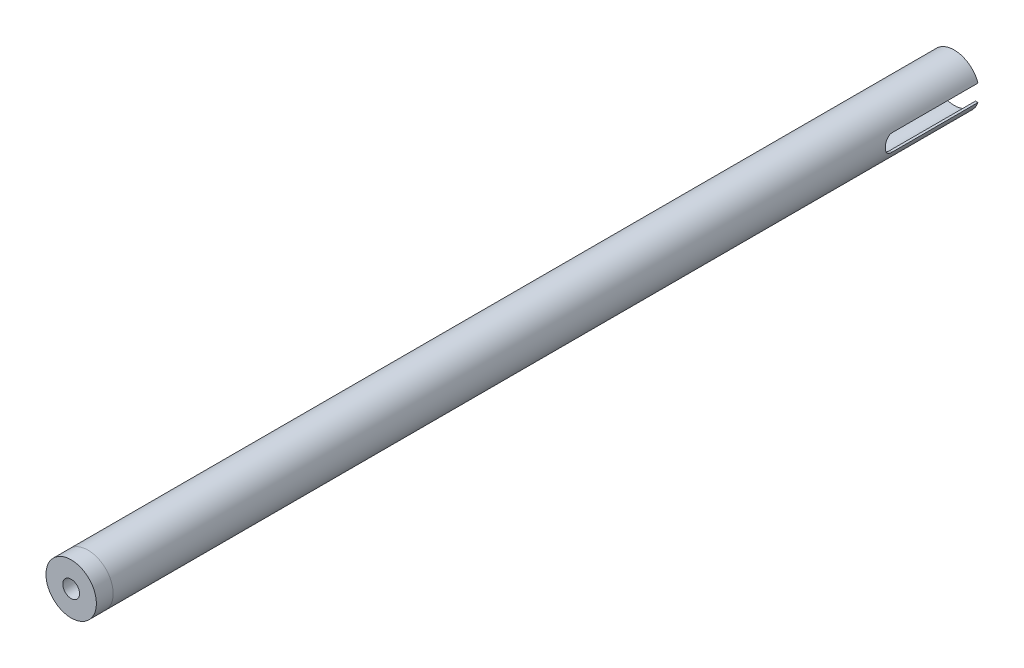
SolidWorks part; units mm, degrees
material "AISI 4130 Steel, normalized at 870C"
ref_plane "Front Plane" through (0, 0, 0) normal (0, 0, 1) x (1, 0, 0)
ref_plane "Top Plane" through (0, 0, 0) normal (0, 1, 0) x (1, 0, 0)
ref_plane "Right Plane" through (0, 0, 0) normal (1, 0, 0) x (0, 0, -1)
sketch "Axis" plane through (0, 0, 0) normal (0, 1, 0) x (1, 0, 0)
  line L0 (0, 0) -> (0, 333.5712) construction
  line L1 (0, 0) -> (0, -21.9075) construction
  line L2 (0, 333.5712) -> (-9.525, 333.5712) construction
  line L4 (0, 368.0728) -> (-10.3187, 330.6961) construction
  dimension "D1" = 21.9075
  dimension "D2" = 9.525
sketch "Sketch1" plane through (0, 0, 0) normal (0, 0, 1) x (1, 0, 0)
  line L0 (-9.525, 0) -> (9.525, 0) construction
  line L1 (-8.9803, 3.175) -> (8.9803, 3.175)
  line L2 (-8.9803, -3.175) -> (8.9803, -3.175)
  circle A0 centre (0, 0) radius 9.525
  circle A1 centre (0, 0) radius 8.636
  circle A2 centre (0, 0) radius 3.175
  dimension "D1" = 19.05
  dimension "D3" = 6.35
  dimension "D2" = 0.889
  dimension "D4" = 6.35
extrude "Threaded insert 1-1" add sketch "Sketch1" against normal blind 6.35 contours A2 L1 A1 | A1 L1 A0 | A2 L0 A1 L1 | A1 L0 A0 L1 | L0 A1 L2 A0 | L0 A2 L2 A1 | A2 L2 A1 | A1 L2 A0 | L0 A1 L2 A2 | L0 A0 L2 A1 | A0 L0 A1 L1 | A1 L0 A2 L1 region at (5.4259, 1.6615, 0) region at (5.4259, -1.6615, 0) region at (8.8881, 1.6046, 0) region at (8.8881, -1.6046, 0) region at (-5.4259, -1.6615, 0) region at (-5.4259, 1.6615, 0) region at (0, 5.4321, 0) region at (0, -5.4321, 0) region at (0, 8.8265, 0) region at (8.5057, -3.3655, 0) region at (-8.8881, -1.6046, 0) region at (-8.8881, 1.6046, 0)
extrude "Threaded insert 1-2" add sketch "Sketch1<3>" against normal blind 6.35 from surface contours A2 L1 A1 | A2 L0 A1 L1 | L0 A2 L2 A1 | A2 L2 A1 | L0 A1 L2 A2 | A1 L0 A2 L1 region at (5.4259, 1.6615, 0) region at (5.4259, -1.6615, 0) region at (-5.4259, -1.6615, 0) region at (-5.4259, 1.6615, 0) region at (0, 5.4321, 0) region at (0, -5.4321, 0) starting at face at (9.525, 0, -6.35)
sketch "Sketch1<3>" plane through (0, 0, 0) normal (0, 0, 1) x (1, 0, 0) same geometry as "Sketch1"
extrude "A-arm tube" add sketch "Sketch1<4>" against normal up to vertex (333.5712 mm away) from surface separate body contours A1 L1 A0 | A1 L0 A0 L1 | L0 A1 L2 A0 | A1 L2 A0 | L0 A0 L2 A1 | A0 L0 A1 L1 region at (8.8881, 1.6046, 0) region at (8.8881, -1.6046, 0) region at (0, 8.8265, 0) region at (8.5057, -3.3655, 0) region at (-8.8881, -1.6046, 0) region at (-8.8881, 1.6046, 0) up to point (0, 0, -333.5712) starting at face at (8.636, 0, -6.35)
sketch "Sketch1<4>" plane through (0, 0, 0) normal (0, 0, 1) x (1, 0, 0) same geometry as "Sketch1"
extrude "Apex slot" cut sketch "Sketch1<5>" along normal blind 35.56 from surface contours A0 L0 A1 L1 | L0 A0 L2 A1 | A1 L0 A0 L1 | L0 A1 L2 A0 region at (8.8881, 1.6046, 0) region at (8.8881, -1.6046, 0) region at (-8.8881, -1.6046, 0) region at (-8.8881, 1.6046, 0) starting at face at (8.636, 0, -333.5712)
sketch "Sketch1<5>" plane through (0, 0, 0) normal (0, 0, 1) x (1, 0, 0) same geometry as "Sketch1"
fillet "Fillet1" radius 3.175 4 edges at (-8.5057, 3.175, -298.0112) (-8.5057, -3.175, -298.0112) (8.5057, -3.175, -298.0112) (8.5057, 3.175, -298.0112)
equation "\"tube diameter\"= 3 / 4"
equation "\"tube thickness\"= .035"
equation "\"apex thickness\"= .25"
equation "\"tube slot\"= 1.4"
equation "\"D1@Sketch1\"=\"tube diameter\""
equation "\"D2@Sketch1\"=\"tube thickness\""
equation "\"threaded insert hole\"= 1 / 4"
equation "\"D3@Sketch1\"=\"threaded insert hole\""
equation "\"D4@Sketch1\"=\"apex thickness\""
equation "\"D1@Apex slot\" = \"tube slot\""
equation "\"D1@Fillet1\"=\"apex thickness\"/2"
equation "\"D2@Axis\"=\"tube diameter\"/2"
